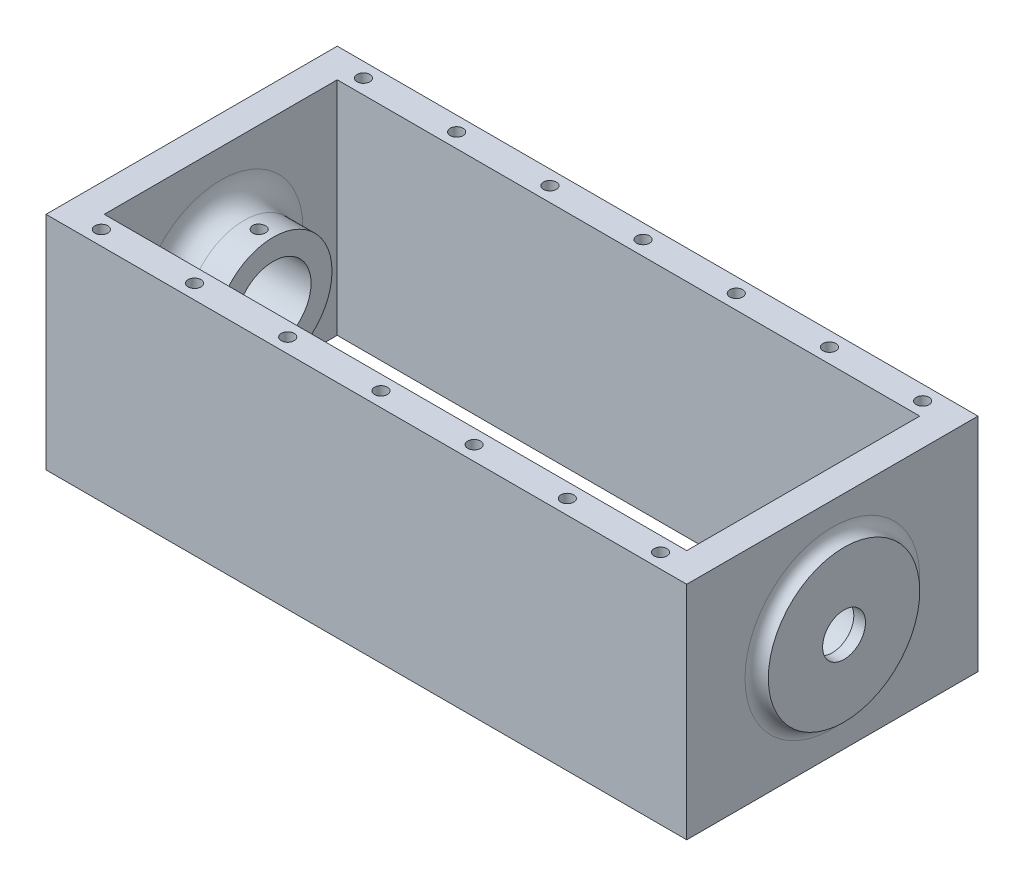
SolidWorks part; units mm, degrees
ref_plane "Front Plane" through (0, 0, 0) normal (0, 0, 1) x (1, 0, 0)
ref_plane "Top Plane" through (0, 0, 0) normal (0, 1, 0) x (1, 0, 0)
ref_plane "Right Plane" through (0, 0, 0) normal (1, 0, 0) x (0, 0, -1)
sketch "Sketch1" plane through (0, 0, 0) normal (0, 1, 0) x (1, 0, 0)
  line L1 (0, 0) -> (139.7, 0)
  line L2 (0, 0) -> (0, 63.5)
  line L3 (0, 63.5) -> (139.7, 63.5)
  line L4 (139.7, 0) -> (139.7, 63.5)
  dimension "D1" = 139.7
  dimension "D2" = 63.5
extrude "Boss-Extrude1" add sketch "Sketch1" along normal blind 3.81
sketch "Sketch2" plane through (0, 3.81, 0) normal (0, 1, 0) x (1, 0, 0)
  line L0 (139.7, 0) -> (139.7, 63.5) construction
  line L1 (133.35, 57.15) -> (6.35, 57.15)
  line L2 (133.35, 57.15) -> (133.35, 6.35)
  line L3 (133.35, 6.35) -> (6.35, 6.35)
  line L4 (6.35, 57.15) -> (6.35, 6.35)
  line L5 (0, 63.5) -> (0, 0) construction
  line L6 (0, 0) -> (139.7, 0) construction
  line L7 (139.7, 63.5) -> (0, 63.5) construction
  line M5 (0, 63.5) -> (0, 0)
  line M6 (0, 0) -> (139.7, 0)
  line M7 (139.7, 0) -> (139.7, 63.5)
  line M8 (139.7, 63.5) -> (0, 63.5)
  dimension "D1" = 6.35
  dimension "D2" = 6.35
  dimension "D3" = 6.35
  dimension "D4" = 6.35
extrude "Boss-Extrude2" add sketch "Sketch2" along normal blind 48.26 contours L4 L1 L2 L3 M8 M5 M6 M7 region at (69.85, 3.81, -61.9655)
sketch "Sketch3" plane through (139.7, 0, 0) normal (1, 0, 0) x (0, 0, -1)
  line L0 (31.75, 52.07) -> (31.75, 0) construction
  line L1 (0, 52.07) -> (63.5, 52.07) construction
  line L2 (0, 0) -> (63.5, 0) construction
  line L3 (0, 27.94) -> (63.5, 27.94) construction
  line L6 (0, 52.07) -> (0, 0) construction
  line L7 (63.5, 52.07) -> (63.5, 0) construction
  circle A1 centre (31.75, 27.94) radius 8.255
  dimension "D2" = 16.51
  dimension "D1" = 24.13
extrude "Cut-Extrude1" cut sketch "Sketch3" against normal blind 150.114
sketch "Sketch4" plane through (0, 0, 0) normal (0, -1, 0) x (1, 0, 0)
  line L1 (139.7, 0) -> (0, 0)
  line L2 (139.7, 0) -> (139.7, -63.5)
  line L3 (139.7, -63.5) -> (0, -63.5)
  line L4 (0, 0) -> (0, -63.5)
extrude "Cut-Extrude2" cut sketch "Sketch4" against normal blind 3.81
sketch "Sketch5" plane through (133.35, 0, 0) normal (-1, 0, 0) x (0, 0, 1)
  circle A1 centre (-31.75, 27.94) radius 8.255
  circle A2 centre (-31.75, 27.94) radius 12.7
  dimension "D1" = 25.4
extrude "Boss-Extrude3" add sketch "Sketch5" along normal blind 11.43
fillet "Fillet1" radius 5.08 1 edges at (133.35, 27.94, -44.45)
sketch "Sketch6" plane through (6.35, 0, 0) normal (1, 0, 0) x (0, 0, -1)
  circle A0 centre (31.75, 27.94) radius 8.255
  circle A1 centre (31.75, 27.94) radius 12.827
  dimension "D1" = 4.572
extrude "Boss-Extrude4" add sketch "Sketch6" along normal blind 11.43
fillet "Fillet2" radius 5.08 1 edges at (6.35, 27.94, -44.577)
ref_plane "Plane1" through (0, 40.767, 0) normal (0, 1, 0) x (1, 0, 0)
sketch "Sketch7" plane through (0, 40.767, 0) normal (0, 1, 0) x (1, 0, 0)
  line L0 (17.78, 18.923) -> (17.78, 44.577) construction
  line L1 (0, 0) -> (139.7, 0) construction
  circle A0 centre (14.732, 31.75) radius 1.4
  dimension "D1" = 2.8
  dimension "D2" = 3.048
  dimension "D3" = 31.75
extrude "Cut-Extrude3" cut sketch "Sketch7" against normal through all
sketch "Sketch8" plane through (0, 40.767, 0) normal (0, 1, 0) x (1, 0, 0)
  line L0 (121.92, 44.45) -> (121.92, 19.05) construction
  line L1 (139.7, 63.5) -> (0, 63.5) construction
  circle A0 centre (124.968, 31.75) radius 1.4
  dimension "D3" = 2.8
  dimension "D1" = 3.048
  dimension "D2" = 31.75
extrude "Cut-Extrude4" cut sketch "Sketch8" against normal through all
sketch "Sketch9" plane through (0, 0, 0) normal (-1, 0, 0) x (0, 0, 1)
  circle A0 centre (-31.75, 27.94) radius 16.51
  circle A1 centre (-31.75, 27.94) radius 4.6745
extrude "Boss-Extrude5" add sketch "Sketch9" along normal blind 2.54
fillet "Fillet3" radius 2.54 1 edges at (0, 27.94, -48.26)
sketch "Sketch10" plane through (139.7, 0, 0) normal (1, 0, 0) x (0, 0, -1)
  circle A0 centre (31.75, 27.94) radius 16.51
  circle A2 centre (31.75, 27.94) radius 4.6745
extrude "Boss-Extrude6" add sketch "Sketch10" along normal blind 2.54
fillet "Fillet4" radius 2.54 1 edges at (139.7, 27.94, -15.24)
sketch "Sketch11" plane through (0, 52.07, 0) normal (0, 1, 0) x (1, 0, 0)
  line L0 (69.85, 63.5) -> (69.85, 57.15) construction
  line L1 (139.7, 63.5) -> (0, 63.5) construction
  line L2 (133.35, 57.15) -> (6.35, 57.15) construction
  line L3 (69.85, 57.15) -> (69.85, 60.325) construction
  line L4 (69.85, 60.325) -> (139.7, 60.325) construction
  line L5 (139.7, 0) -> (139.7, 63.5) construction
  line L6 (139.7, 60.325) -> (0, 60.325) construction
  line L7 (0, 63.5) -> (0, 0) construction
  line L8 (69.85, 6.35) -> (69.85, 0) construction
  line L9 (133.35, 6.35) -> (6.35, 6.35) construction
  line L10 (0, 0) -> (139.7, 0) construction
  line L11 (69.85, 0) -> (69.85, 3.175) construction
  line L12 (69.85, 3.175) -> (139.7, 3.175) construction
  line L13 (139.7, 0) -> (139.7, 63.5) construction
  line L14 (139.7, 3.175) -> (0, 3.175) construction
  line L15 (0, 63.5) -> (0, 0) construction
  line L16 (49.53, 60.325) -> (119.38, 60.325) construction
  line L17 (29.21, 60.325) -> (99.06, 60.325) construction
  line L18 (8.89, 60.325) -> (78.74, 60.325) construction
  line L19 (90.17, 60.325) -> (160.02, 60.325) construction
  line L20 (110.49, 60.325) -> (180.34, 60.325) construction
  line L21 (130.81, 60.325) -> (200.66, 60.325) construction
  circle A0 centre (69.85, 60.325) radius 1.4
  circle A1 centre (69.85, 3.175) radius 1.4
  circle A2 centre (49.53, 60.325) radius 1.4
  circle A3 centre (29.21, 60.325) radius 1.4
  circle A4 centre (8.89, 60.325) radius 1.4
  circle A5 centre (90.17, 60.325) radius 1.4
  circle A6 centre (110.49, 60.325) radius 1.4
  circle A7 centre (130.81, 60.325) radius 1.4
  circle A8 centre (90.17, 3.175) radius 1.4
  circle A9 centre (110.49, 3.175) radius 1.4
  circle A10 centre (130.81, 3.175) radius 1.4
  circle A11 centre (49.53, 3.175) radius 1.4
  circle A12 centre (29.21, 3.175) radius 1.4
  circle A13 centre (8.89, 3.175) radius 1.4
  dimension "D1" = 2.8
  dimension "D2" = 2.8
  dimension "D3" = 4
  dimension "D4" = 4
  dimension "D5" = 4
  dimension "D6" = 4
extrude "Cut-Extrude5" cut sketch "Sketch11" against normal blind 3.81
ref_plane "Plane2" through (0, 27.94, 0) normal (0, 1, 0) x (1, 0, 0)
mirror "Mirror1" about plane through (0, 27.94, 0) normal (0, 1, 0) of "Cut-Extrude5"
